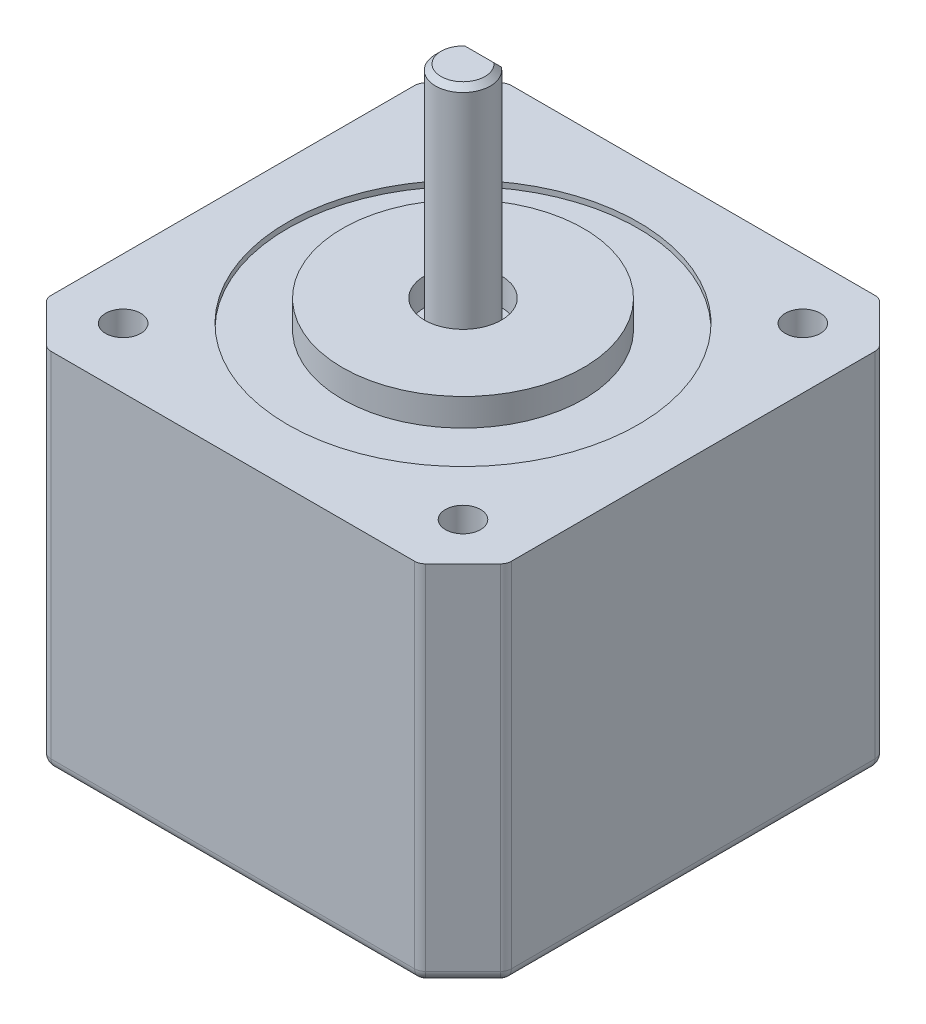
SolidWorks part; units mm, degrees
ref_plane "Front" through (0, 0, 0) normal (0, 0, 1) x (1, 0, 0)
ref_plane "Top" through (0, 0, 0) normal (0, 1, 0) x (1, 0, 0)
ref_plane "Right" through (0, 0, 0) normal (1, 0, 0) x (0, 0, -1)
sketch "Sketch1" plane through (0, 0, 0) normal (0, 1, 0) x (1, 0, 0)
  line L1 (0, 0) -> (42, 0)
  line L2 (0, 0) -> (0, 42)
  line L3 (0, 42) -> (42, 42)
  line L4 (42, 0) -> (42, 42)
  dimension "D1" = 42
extrude "Boss-Extrude1" add sketch "Sketch1" along normal blind 33.2
chamfer "Chamfer1" distance 4 angle 45 4 edges at (0, 16.6, -42) (42, 16.6, -42) (0, 16.6, 0) (42, 16.6, 0)
sketch "Sketch2" plane through (0, 33.2, 0) normal (0, 1, 0) x (1, 0, 0)
  line L0 (42, 21) -> (0, 21) construction
  line L1 (42, 4) -> (42, 38) construction
  line L2 (0, 38) -> (0, 4) construction
  circle A0 centre (21, 21) radius 16
  dimension "D1" = 32
extrude "Cut-Extrude1" cut sketch "Sketch2" against normal blind 0.5
sketch "Sketch3" plane through (0, 32.7, 0) normal (0, 1, 0) x (1, 0, 0)
  circle A0 centre (21, 21) radius 11
  dimension "D1" = 22
extrude "Boss-Extrude3" add sketch "Sketch3" along normal blind 2.5
sketch "Sketch4" plane through (0, 35.2, 0) normal (0, 1, 0) x (1, 0, 0)
  circle A0 centre (21, 21) radius 3.5
  dimension "D1" = 7
extrude "Cut-Extrude2" cut sketch "Sketch4" against normal blind 2.5
sketch "Sketch7" plane through (0, 0, 0) normal (0, -1, 0) x (1, 0, 0)
  line L0 (21, -42) -> (21, 0) construction
  line L1 (38, -42) -> (4, -42) construction
  line L2 (4, 0) -> (38, 0) construction
  circle A0 centre (21, -21.1686) radius 5.5
  dimension "D1" = 11
extrude "Cut-Extrude4" cut sketch "Sketch7" against normal blind 4
sketch "Sketch5" plane through (0, 32.7, 0) normal (0, 1, 0) x (1, 0, 0)
  circle A0 centre (21, 21) radius 2.5
  dimension "D1" = 5
extrude "Boss-Extrude4" add sketch "Sketch5" along normal blind 21
sketch "Sketch6" plane through (0, 53.7, 0) normal (0, 1, 0) x (1, 0, 0)
  line L0 (19.5, 23) -> (22.5, 23)
  circle A0 centre (21, 21) radius 2.5 construction
  arc A1 (22.5, 23) -> (19.5, 23) centre (21, 21) ccw
  dimension "D1" = 3
extrude "Cut-Extrude3" cut sketch "Sketch6" against normal blind 16
chamfer "Chamfer2" distance 0.5 angle 45 2 edges at (21, 53.7, -23) (21, 53.7, -18.5)
sketch "Sketch8" plane through (0, 33.2, 0) normal (0, 1, 0) x (1, 0, 0)
  line L0 (21, 42) -> (21, 0) construction
  line L1 (38, 42) -> (4, 42) construction
  line L2 (4, 0) -> (38, 0) construction
  line L3 (21, 0) -> (42, 21) construction
  line L4 (42, 4) -> (42, 38) construction
  line L5 (42, 21) -> (0, 21) construction
  line L6 (0, 38) -> (0, 4) construction
  line L7 (0, 21) -> (5.5, 36.5) construction
  line L8 (5.5, 36.5) -> (36.5, 36.5) construction
  line L9 (36.5, 36.5) -> (36.5, 5.5) construction
  line L10 (36.5, 5.5) -> (5.5, 5.5) construction
  line L11 (5.5, 5.5) -> (5.5, 36.5) construction
  circle A0 centre (5.5, 36.5) radius 1.6
  circle A1 centre (36.5, 36.5) radius 1.6
  circle A2 centre (36.5, 5.5) radius 1.6
  circle A3 centre (5.5, 5.5) radius 1.6
  point P16 (21, 36.5)
  point P17 (36.5, 21)
  dimension "D2" = 3.2
  dimension "D1" = 31
extrude "Cut-Extrude5" cut sketch "Sketch8" against normal blind 6
sketch "Sketch9" plane through (0, 0, -42) normal (0, 0, -1) x (-1, 0, 0)
  line L0 (-21, 0) -> (-21, 33.2) construction
  line L1 (-38, 0) -> (-4, 0) construction
  line L2 (-38, 33.2) -> (-4, 33.2) construction
  line L4 (-25, 2.3) -> (-17, 2.3)
  line L5 (-25, 2.3) -> (-25, 9.3)
  line L6 (-25, 9.3) -> (-17, 9.3)
  line L7 (-17, 2.3) -> (-17, 9.3)
  point P10 (-21, 2.3)
  dimension "D1" = 7
  dimension "D2" = 8
  dimension "D3" = 2.3
extrude "Cut-Extrude6" cut sketch "Sketch9" against normal blind 4
fillet "Fillet1" radius 1 17 edges at (2, 0, -2) (21, 0, 0) (40, 0, -2) (42, 0, -21) (40, 0, -40) (21, 0, -42) (2, 0, -40) (0, 0, -21) (21, 0, -26.6686) (42, 16.6, -38) (38, 16.6, -42) (42, 16.6, -4) (38, 16.6, 0) (4, 16.6, 0) (0, 16.6, -4) (0, 16.6, -38) (4, 16.6, -42)
